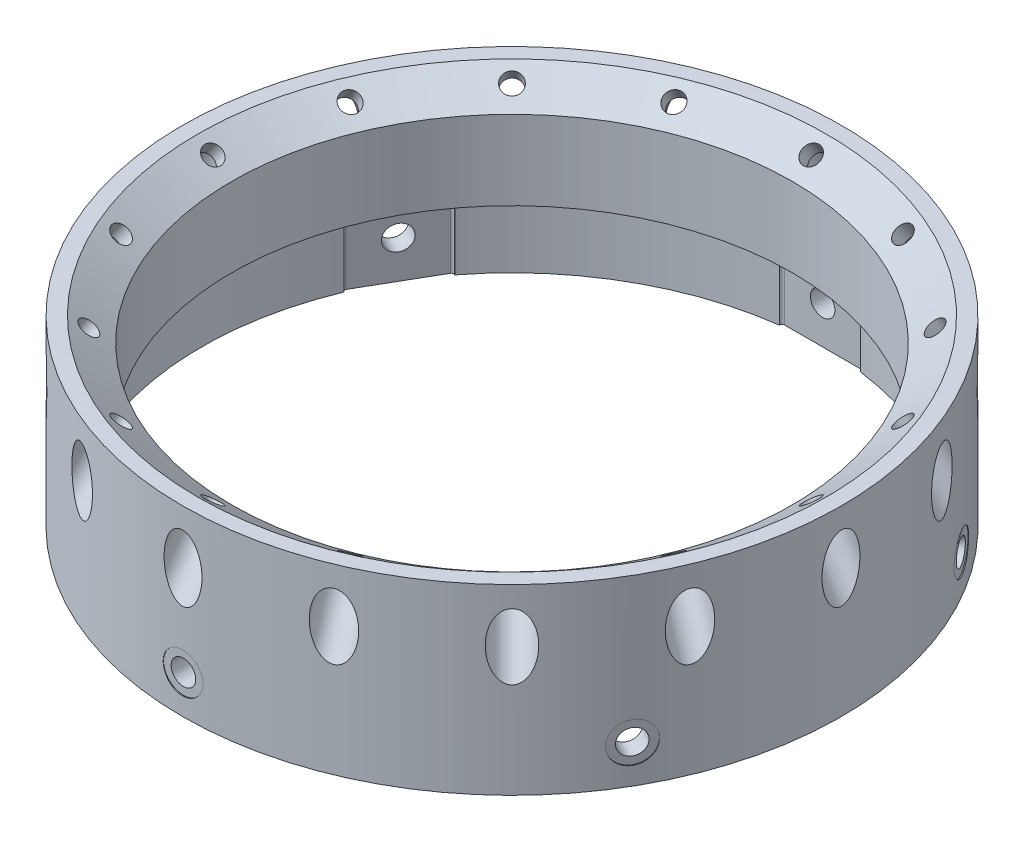
SolidWorks part; units mm, degrees
ref_plane "Front Plane" through (0, 0, 0) normal (0, 0, 1) x (1, 0, 0)
ref_plane "Top Plane" through (0, 0, 0) normal (0, 1, 0) x (1, 0, 0)
ref_plane "Right Plane" through (0, 0, 0) normal (1, 0, 0) x (0, 0, -1)
sketch "Main sketch" plane through (0, 0, 0) normal (0, 0, 1) x (1, 0, 0)
  line L0 (0, 0) -> (-87, 0) construction
  line L23 (-87, 0) -> (-87, 27.1992)
  line L24 (-83, 27.1992) -> (-74, 20.8973)
  line L25 (-74, 20.8973) -> (-74, 0)
  line L26 (-74, 0) -> (-81, 0)
  line L30 (0, 0) -> (0, -35.5238) construction
  line L31 (-87, 27.1992) -> (-83, 27.1992)
  line L32 (-74, 20.8973) -> (-87, 20.8973) construction
  line L33 (-87, 0) -> (-87, -21)
  line L34 (-87, -21) -> (-82, -21)
  line L35 (-82, -21) -> (-82, 0)
  line L36 (-82, 0) -> (-81, 0)
  point P4 (-87, 30)
  dimension "D1" = 87
  dimension "D4" = 55
  dimension "D5" = 30
  dimension "D6" = 13
  dimension "D8" = 4
  dimension "D9" = 90
revolve "Main revolve" add sketch "Main sketch" angle 360 about L30
sketch "Hole position" plane through (0, 0, 0) normal (0, 0, 1) x (1, 0, 0)
  line L0 (-79, 24.3983) -> (-83, 18.6857) construction
  line L1 (-83, 27.1992) -> (-74, 20.8973) construction
  line L2 (0, 30) -> (0, -2.3509) construction
  line L4 (-83, 27.1992) -> (-83, -10.9444) construction
  line L6 (87, 30) -> (-87, 30) construction
  line L7 (-83, 18.6857) -> (-67.2656, 7.6684) construction
  point P7 (-79, 24.3983)
  dimension "D1" = 4
ref_plane "Hole plane" through (-18.5267, -26.4589, 0) normal (-0.5736, -0.8192, 0) x (0.8192, -0.5736, 0)
sketch "Sketch14" plane through (-18.5267, -26.4589, 0) normal (-0.5736, -0.8192, 0) x (0.8192, -0.5736, 0)
  circle A1 centre (-78.7073, 0) radius 5
  dimension "D1" = 5
extrude "Hole extrude 1" cut sketch "Sketch14" against normal blind 3 and the other way through all
hole_wizard "screw extrude" positions "3DSketch13" profile "Sketch15" hole size "Ø5.0" standard "DIN" end condition up to next
sketch3d "3DSketch13"
  line L0 (-79, 24.3983, 0) -> (-83, 18.6857, 0) construction
  point P0 (-81.2793, 21.1432, 0)
sketch "Sketch15" plane through (-81.2793, 21.1432, 0) normal (0, 0, 1) x (0.8192, -0.5736, 0)
  line L0 (0, 0) -> (0, 3.9738)
  line L1 (0, 3.9738) -> (2.5, 3.9738)
  line L2 (2.5, 3.9738) -> (2.5, 0)
  line L5 (2.5, 0) -> (0, 0)
  line L11 (0, -6.35) -> (0, 107.95) construction
  dimension "Thru Hole Dia." = 5
  dimension "Thru Hole Depth" = 3.9738
pattern_circular "Screw holes pattern" count 16 over 360 about axis through (0, 0, 0) along (0, 1, 0) of "Hole extrude 1", "screw extrude" reverse direction yes
ref_plane "Płaszczyzna1" through (16.9729, 0, 85.3283) normal (0.1951, 0, 0.9808) x (0, 1, 0)
sketch "Szkic14" plane through (0, 0, 0) normal (0, 0, 1) x (1, 0, 0)
  line L0 (0, -21) -> (0, -11)
  line L1 (-87, -21) -> (87, -21) construction
  circle A0 centre (0, -11) radius 3.25
  dimension "D1" = 6.5
extrude "Wytnij-wyciągnięcie3" cut sketch "Szkic14" against normal up to next contours A0 region at (2.2331, -13.2331, 0)
pattern_circular "Szyk kołowy2" count 6 over 360 about axis through (0, -21, 0) along (0, 1, 0) of "Wytnij-wyciągnięcie3"
ref_plane "Plane1" through (0, 0, 87) normal (0, 0, 1) x (1, 0, 0)
sketch "Sketch16" plane through (0, 0, 87) normal (0, 0, 1) x (1, 0, 0)
  circle A0 centre (0, -11) radius 3.25 construction
  circle A1 centre (0, -11) radius 3.25
  circle A2 centre (0, -11) radius 5.25
  dimension "D1" = 10.5
extrude "Cut-Extrude1" cut sketch "Sketch16" against normal blind 0.25
pattern_circular "CirPattern1" count 6 over 360 about axis through (0, 0, 0) along (0, 1, 0) of "Cut-Extrude1"
sketch "Sketch17" plane through (0, -21, 0) normal (0, -1, 0) x (1, 0, 0)
  line L4 (10.1, -80.819) -> (10.1, -82.0164)
  line L6 (0, -82.0164) -> (10.1, -82.0164)
  line L7 (0, -82.0164) -> (-10.1, -82.0164)
  line L8 (10.1, -80.819) -> (0, -80.819)
  line L9 (0, -80.819) -> (-10.1, -80.819)
  line L10 (-10.1, -80.819) -> (-10.1, -82.0164)
extrude "Cut-Extrude2" cut sketch "Sketch17" against normal blind 21
pattern_circular "CirPattern2" count 6 over 360 about axis through (0, 0, 0) along (0, 1, 0) of "Cut-Extrude2"
sketch "Sketch18" plane through (0, 0, -82.0164) normal (0, 0, 1) x (1, 0, 0)
  line L0 (-10.1, -21) -> (-10.72, -21)
  line L1 (-10.72, -21) -> (-10.72, 0)
  line L2 (-10.72, 0) -> (-10.1, 0)
  line L3 (10.1, 0) -> (10.72, 0)
  line L4 (-10.1, -21) -> (10.1, -21)
  line L5 (10.1, -21) -> (10.1, 0)
  line L6 (10.1, 0) -> (-10.1, 0)
  line L7 (-10.1, 0) -> (-10.1, -21)
  line L8 (-10.1, -21) -> (10.1, -21)
  line L9 (10.1, -21) -> (10.1, 0)
  line L10 (10.1, 0) -> (-10.1, 0)
  line L11 (-10.1, 0) -> (-10.1, -21)
  line L12 (10.72, 0) -> (10.72, -21)
  line L13 (10.72, -21) -> (10.1, -21)
  line M8 (10.1, -21) -> (10.1, 0)
  line M10 (-10.1, 0) -> (-10.1, -21)
  dimension "D2" = 0.62
  dimension "D3" = 0.62
  dimension "D1" = 0
extrude "Cut-Extrude3" cut sketch "Sketch18" along normal blind 10 contours L2 L1 L0 M10 | L13 L12 L3 M8 region at (-10.41, -10.5, -82.0164) region at (10.41, -10.5, -82.0164)
fillet "Fillet1" radius 0.62 2 edges at (10.72, -10.5, -82.0164) (-10.72, -10.5, -82.0164)
pattern_circular "CirPattern3" count 6 over 360 about axis through (0, 0, 0) along (0, 1, 0) of "Fillet1", "Cut-Extrude3"
